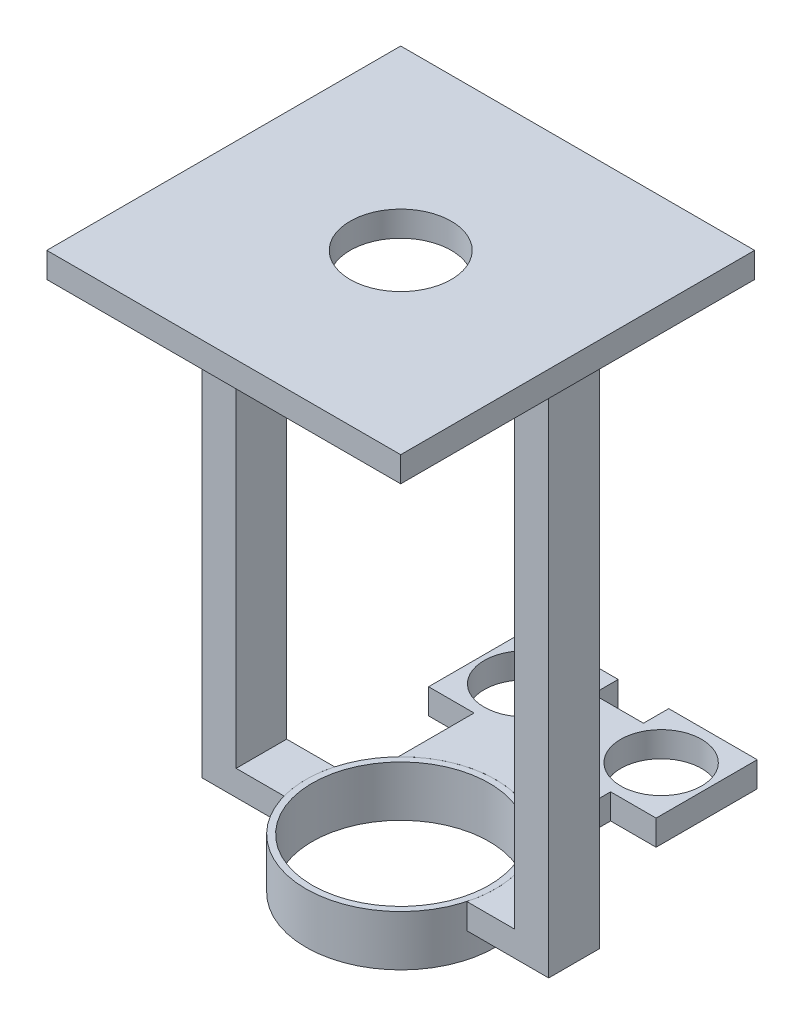
SolidWorks part; units mm, degrees
ref_plane "Front Plane" through (0, 0, 0) normal (0, 0, 1) x (1, 0, 0)
ref_plane "Top Plane" through (0, 0, 0) normal (0, 1, 0) x (1, 0, 0)
ref_plane "Right Plane" through (0, 0, 0) normal (1, 0, 0) x (0, 0, -1)
sketch "Sketch2" plane through (0, 0, 0) normal (0, 1, 0) x (1, 0, 0)
  line L0 (0, 17.5) -> (0, -17.5) construction
  line L1 (-17.5, 0) -> (17.5, 0) construction
  line L2 (-17.5, 0) -> (-17.5, 5) construction
  line L3 (-16.7705, 5) -> (-34.2705, 5)
  line L4 (-34.2705, 5) -> (-34.2705, -5)
  line L5 (-16.7705, -5) -> (-34.2705, -5)
  line L6 (16.7705, -5) -> (34.2705, -5)
  line L7 (34.2705, 5) -> (34.2705, -5)
  line L8 (16.7705, 5) -> (34.2705, 5)
  line L9 (0, 28.012) -> (22.5, 28.012)
  line L10 (22.5, 28.012) -> (22.5, 48.012)
  line L11 (22.5, 48.012) -> (5, 48.012)
  line L12 (-22.5, 48.012) -> (-22.5, 28.012)
  line L13 (-22.5, 28.012) -> (0, 28.012)
  line L14 (22.5, 38.012) -> (21.5, 38.012) construction
  line L20 (-5, 48.012) -> (-22.5, 48.012)
  line L21 (0, 43.012) -> (0, 28.012) construction
  line L22 (-5, 48.012) -> (-5, 43.012)
  line L23 (-5, 43.012) -> (5, 43.012)
  line L24 (5, 43.012) -> (5, 48.012)
  line L25 (13.5, 46.012) -> (13.5, 48.012) construction
  line L26 (13.5, 30.012) -> (13.5, 28.012) construction
  line L27 (-13.5, 38.012) -> (13.5, 38.012) construction
  line L28 (-13.5, 13.012) -> (-13.5, 28.012)
  line L29 (13.5, 28.012) -> (13.5, 13.012)
  line L30 (-18.75, 0) -> (-27.55, 0) construction
  line L31 (-27.55, 5) -> (-27.55, -5)
  line L32 (27.55, 5) -> (27.55, -5)
  circle A0 centre (0, 0) radius 17.5
  circle A1 centre (0, 0) radius 18.75
  circle A2 centre (13.5, 38.012) radius 8
  circle A3 centre (-13.5, 38.012) radius 8
  point P13 (-34.2705, 0)
  point P47 (0, 0)
  point P48 (0, 0)
  dimension "D1" = 35
  dimension "D2" = 17.5
  dimension "D4" = 37.5
  dimension "D8" = 1
  dimension "D9" = 16
  dimension "D3" = 5
  dimension "D5" = 5
  dimension "D6" = 20
  dimension "D7" = 45
  dimension "D10" = 17.5
  dimension "D11" = 8.8
  dimension "D12" = 27
  dimension "D13" = 15
extrude "Connector sleeve" add sketch "Sketch2" along normal blind 5 and the other way blind 5 contours L5 A1 L6 A0 | L8 A1 L3 A0 | L6 A1 L8 A0 | L3 A1 L5 A0 region at (-15.95, 0, -9.0999) region at (-17.8897, 0, 0) region at (-17.4208, 0, 5.3867) region at (17.8897, 0, 0)
ref_plane "Plane2" through (0, 30, 0) normal (0, 1, 0) x (1, 0, 0)
extrude "Sensor holder" add sketch "Sketch2<10>" along normal blind 5 separate body contours L24 L23 L22 L20 L12 L13 L9 L10 L11 A2 A3 | A1 L29 L9 L13 L28 | A1 L3 L31 L5 | L31 L3 L4 L5 | A1 L6 L32 L8 | L8 L32 L6 L7 region at (-30.9103, 0, 0) region at (-23.0354, 0, 0) region at (0, 0, -22.3672) region at (0, 0, -37.1747) region at (23.0354, 0, 0) region at (30.9103, 0, 0)
sketch "Sketch2<10>" plane through (0, 0, 0) normal (0, 1, 0) x (1, 0, 0) same geometry as "Sketch2"
extrude "Boss-Extrude1" add sketch "Sketch2<18>" along normal blind 100 contours L31 L3 L4 L5 | L8 L32 L6 L7 region at (-30.9103, 0, 0) region at (30.9103, 0, 0)
sketch "Sketch2<18>" plane through (0, 0, 0) normal (0, 1, 0) x (1, 0, 0) same geometry as "Sketch2"
sketch "Sketch4" plane through (0, 100, 0) normal (0, 1, 0) x (1, 0, 0)
  line L1 (-35, -35) -> (35, -35)
  line L2 (-35, -35) -> (-35, 35)
  line L3 (-35, 35) -> (35, 35)
  line L4 (35, -35) -> (35, 35)
  line L5 (-35, -35) -> (35, 35) construction
  line L6 (-35, 35) -> (35, -35) construction
  circle A0 centre (0, 0) radius 10
  point P0 (0, 0)
  dimension "D2" = 20
  dimension "D1" = 70
extrude "Boss-Extrude2" add sketch "Sketch4" along normal blind 5
